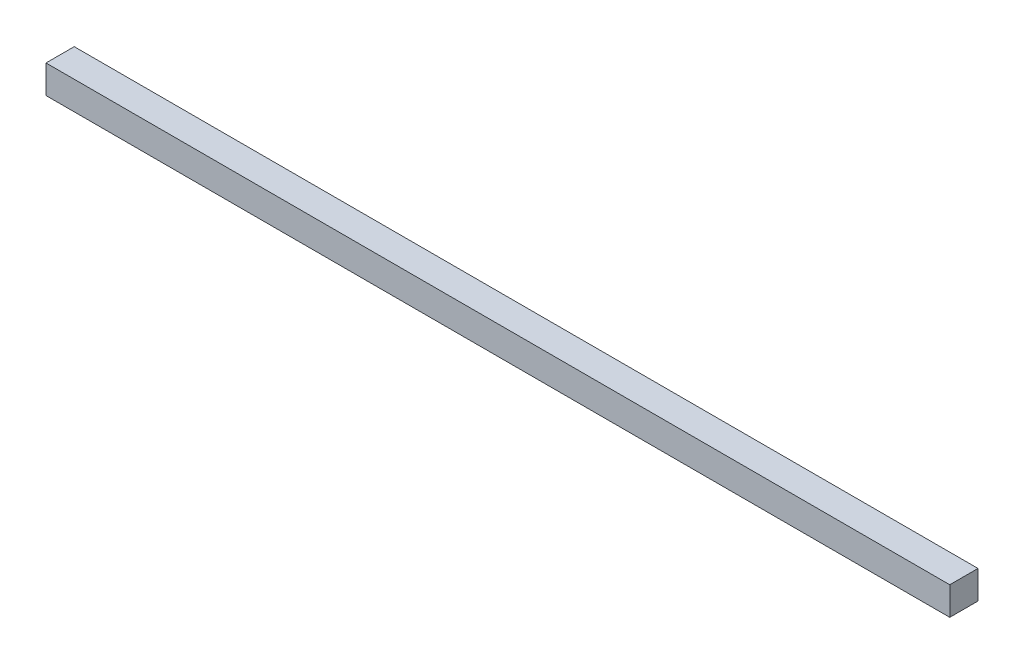
SolidWorks part; units mm, degrees
material "Cedar"
ref_plane "Front Plane" through (0, 0, 0) normal (0, 0, 1) x (1, 0, 0)
ref_plane "Top Plane" through (0, 0, 0) normal (0, 1, 0) x (1, 0, 0)
ref_plane "Right Plane" through (0, 0, 0) normal (1, 0, 0) x (0, 0, -1)
sketch "Sketch1" plane through (0, 0, 0) normal (1, 0, 0) x (0, 0, -1)
  line L1 (-19.05, -19.05) -> (19.05, -19.05)
  line L2 (-19.05, -19.05) -> (-19.05, 19.05)
  line L3 (-19.05, 19.05) -> (19.05, 19.05)
  line L4 (19.05, -19.05) -> (19.05, 19.05)
  line L5 (-19.05, -19.05) -> (19.05, 19.05) construction
  line L6 (-19.05, 19.05) -> (19.05, -19.05) construction
  point P0 (0, 0)
  dimension "D1" = 38.1
  dimension "D2" = 38.1
extrude "Boss-Extrude1" add sketch "Sketch1" along normal blind 609.6 and the other way blind 609.6
